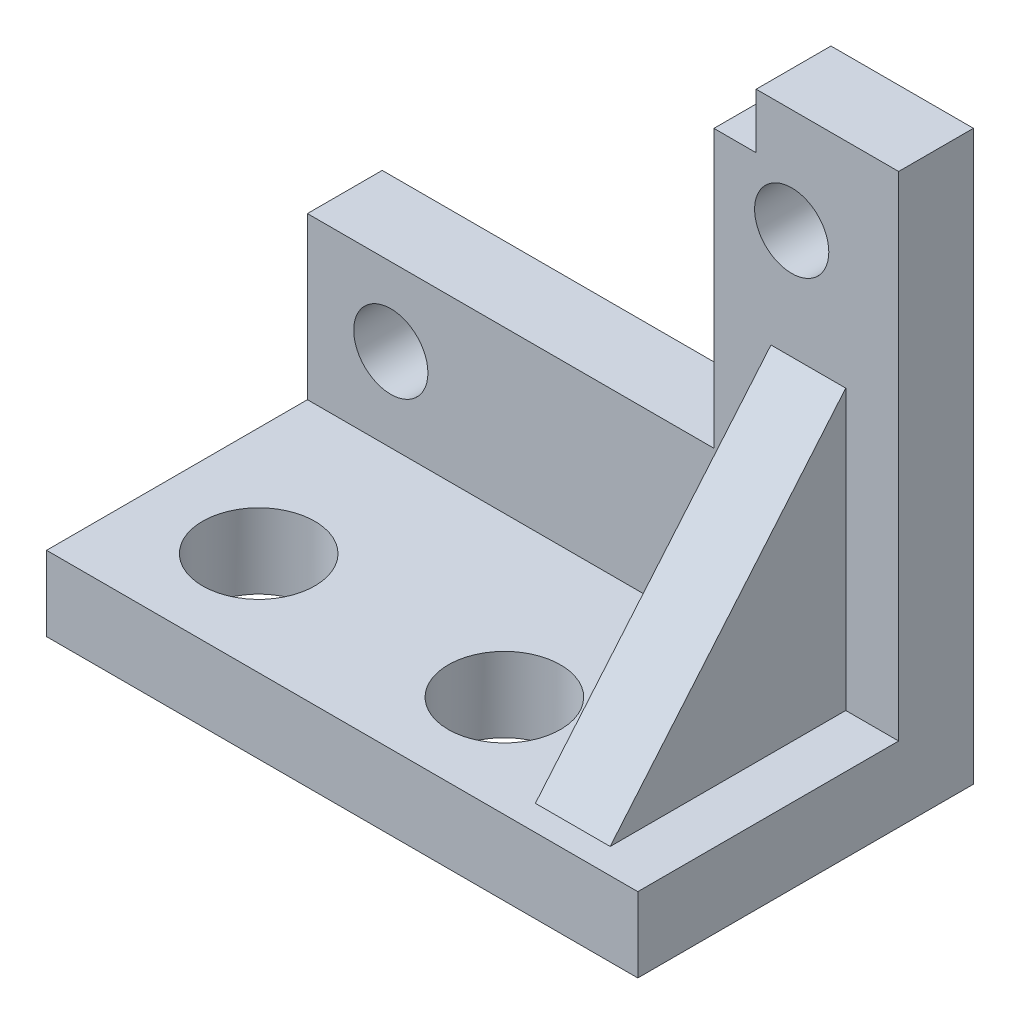
SolidWorks part; units mm, degrees
ref_plane "Front Plane" through (0, 0, 0) normal (0, 0, 1) x (1, 0, 0)
ref_plane "Top Plane" through (0, 0, 0) normal (0, 1, 0) x (1, 0, 0)
ref_plane "Right Plane" through (0, 0, 0) normal (1, 0, 0) x (0, 0, -1)
sketch "Sketch2" plane through (0, 0, 0) normal (0, 0, 1) x (1, 0, 0)
  line L0 (4.3952, 7.8274) -> (4.3952, -1.4384)
  line L1 (4.3952, -1.4384) -> (-11.8608, -1.4384)
  line L2 (-11.8608, -1.4384) -> (-11.8608, -8.2804)
  line L3 (-11.8608, -8.2804) -> (12.2372, -8.2804)
  line L4 (12.2372, -8.2804) -> (12.2372, 12.6586)
  line L5 (12.2372, 12.6586) -> (7.6972, 12.6586)
  line L7 (7.6972, 12.6586) -> (6.1882, 12.6586)
  line L8 (-11.8608, -1.4384) -> (-12.8608, -1.4384)
  line L9 (-11.8608, -1.4384) -> (-11.8608, -8.2804)
  line L10 (-11.8608, -8.2804) -> (-12.8608, -8.2804)
  line L11 (-12.8608, -1.4384) -> (-12.8608, -8.2804)
  line L12 (4.3952, 10.3218) -> (4.3952, 7.8274)
  line L13 (4.3952, 10.3218) -> (6.1882, 10.3218)
  line L14 (6.1882, 10.3218) -> (6.1882, 12.6586)
  circle A0 centre (7.6972, 8.2136) radius 1.5748
  circle A1 centre (-9.3208, -4.7404) radius 1.5748
  point P0 (6.4597, 9.1875)
  dimension "D5" = 16.494
  dimension "D1" = 1
  dimension "D2" = 6.842
  dimension "D3" = 20.939
  dimension "D4" = 24.098
  dimension "D6" = 2.54
  dimension "D7" = 3.54
  dimension "D8" = 17.018
extrude "Boss-Extrude1" add sketch "Sketch2" along normal blind 3.175 contours A0 | L3 L4 L5 L7 L14 L13 L12 L0 L1 L2 | A1 region at (7.6972, 8.2136, 0)
sketch "Sketch5" plane through (0, 0, 0) normal (0, 0, -1) x (-1, 0, 0)
  line L1 (-12.2372, -8.2804) -> (11.8608, -8.2804)
  line L2 (-12.2372, -8.2804) -> (-12.2372, -11.4554)
  line L3 (-12.2372, -11.4554) -> (11.8608, -11.4554)
  line L4 (11.8608, -8.2804) -> (11.8608, -11.4554)
  line L5 (11.8608, -1.4384) -> (11.8608, -8.2804) construction
  dimension "D1" = 3.175
extrude "Boss-Extrude2" add sketch "Sketch5" against normal blind 19.05
sketch "Sketch7" plane through (0, 0, 3.175) normal (0, 0, 1) x (1, 0, 0)
  line L0 (-11.8608, -1.4384) -> (-11.8608, -8.2804) construction
  line L1 (-11.8608, -1.4384) -> (-12.8608, -1.4384)
  line L2 (-11.8608, -1.4384) -> (-11.8608, -8.2804)
  line L3 (-11.8608, -8.2804) -> (-12.8608, -8.2804)
  line L4 (-12.8608, -1.4384) -> (-12.8608, -8.2804)
  dimension "D1" = 1
extrude "Boss-Extrude3" add sketch "Sketch7" against normal blind 3.175
sketch "Sketch8" plane through (0, 0, 19.05) normal (0, 0, 1) x (1, 0, 0)
  line L1 (-11.8608, -11.4554) -> (-12.8608, -11.4554)
  line L2 (-11.8608, -11.4554) -> (-11.8608, -8.2804)
  line L3 (-11.8608, -8.2804) -> (-12.8608, -8.2804)
  line L4 (-12.8608, -11.4554) -> (-12.8608, -8.2804)
extrude "Boss-Extrude4" add sketch "Sketch8" against normal blind 19.05
sketch "Sketch9" plane through (0, 0, 3.175) normal (0, 0, 1) x (1, 0, 0)
  line L0 (6.8165, -8.2804) -> (9.9915, -8.2804)
  line L1 (9.9915, -8.2804) -> (9.9915, 3.57)
  line L2 (-12.8608, -8.2804) -> (12.2372, -8.2804) construction
  line L3 (9.9915, 3.57) -> (6.8165, 3.57)
  line L4 (6.8165, 3.57) -> (6.8165, -8.2804)
  line L6 (12.2372, -8.2804) -> (12.2372, 12.6586) construction
  dimension "D1" = 3.175
  dimension "D2" = 2.2457
extrude "Boss-Extrude5" add sketch "Sketch9" along normal blind 10
sketch "Sketch10" plane through (9.9915, 0, 0) normal (1, 0, 0) x (0, 0, -1)
  line L0 (-3.175, 3.57) -> (-13.175, -8.2804)
  line L1 (-3.175, 3.57) -> (-13.175, 3.57)
  line L2 (-13.175, 3.57) -> (-13.175, -8.2804)
extrude "Cut-Extrude1" cut sketch "Sketch10" against normal through all
sketch "Sketch11" plane through (0, -8.2804, 0) normal (0, 1, 0) x (1, 0, 0)
  line L7 (-8.2367, -12.2485) -> (-8.2367, -14.2485)
  line L8 (-8.2367, -14.2485) -> (-14.967, -14.2485)
  line L9 (-8.2367, -14.2485) -> (13.7986, -14.2485)
  line L11 (-8.2367, -19.6992) -> (13.7986, -19.6992)
  line L12 (13.7986, -14.2485) -> (13.7986, -19.6992)
  line L13 (-14.967, -14.2485) -> (-14.967, -19.6992)
  line L14 (-14.967, -19.6992) -> (-8.2367, -19.6992)
  circle A0 centre (-8.2367, -9.8673) radius 2.3813
  circle A1 centre (2.2559, -9.9305) radius 2.3813
  line M4 (-12.8608, -3.175) -> (-12.8608, -19.05)
  line M5 (-12.8608, -19.05) -> (12.2372, -19.05)
  line M6 (12.2372, -19.05) -> (12.2372, -3.175)
  dimension "D1" = 10.4925
  dimension "D2" = 4.3812
extrude "Cut-Extrude5" cut sketch "Sketch11" against normal blind 10 contours A0 | L9 L8 M4 M5 M6 | A1 region at (-0.3118, -8.2804, 16.6493) region at (-8.2367, -8.2804, 9.8673) region at (2.2559, -8.2804, 9.9305)
